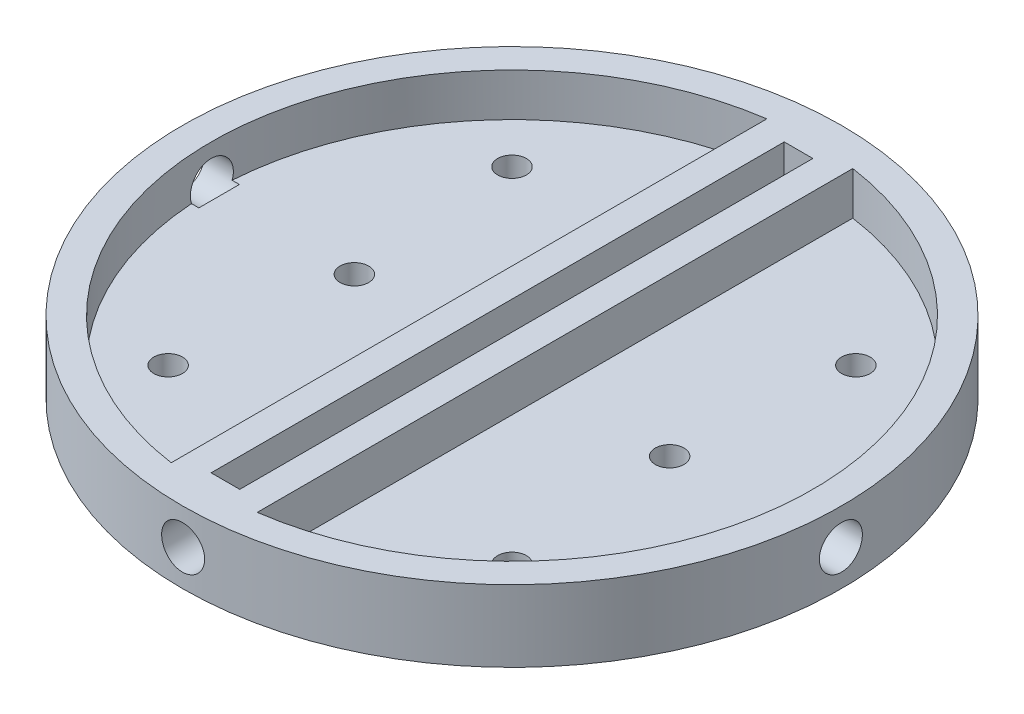
SolidWorks part; units mm, degrees
material "ABS"
ref_plane "Front Plane" through (0, 0, 0) normal (0, 0, 1) x (1, 0, 0)
ref_plane "Top Plane" through (0, 0, 0) normal (0, 1, 0) x (1, 0, 0)
ref_plane "Right Plane" through (0, 0, 0) normal (1, 0, 0) x (0, 0, -1)
sketch "Sketch17" plane through (0, 0, 0) normal (0, 0, 1) x (1, 0, 0)
  line L0 (0, 36.6652) -> (0, -18.0015)
sketch "Sketch5" plane through (0, 0, 0) normal (0, 1, 0) x (1, 0, 0)
  circle A0 centre (0, 0) radius 73.025
  circle A1 centre (38.1, 38.1) radius 3.175
  circle A2 centre (38.1, -38.1) radius 3.175
  circle A3 centre (-38.1, 38.1) radius 3.175
  circle A4 centre (-38.1, -38.1) radius 3.175
extrude "PlateBase" add sketch "Sketch5" along normal blind 6.35
sketch "Sketch6" plane through (0, 6.35, 0) normal (0, 1, 0) x (1, 0, 0)
  line L1 (3.175, 0) -> (3.175, 72.9559)
  line L3 (3.175, 0) -> (3.175, -72.9559)
  line L4 (0, 0) -> (3.175, 0)
  line L5 (-3.175, 0) -> (-3.175, 72.9559)
  line L6 (-9.525, 0) -> (-9.525, 72.4011)
  line L7 (-9.525, 0) -> (-9.525, -72.4011)
  line L8 (-3.175, 0) -> (-3.175, -72.9559)
  line L9 (9.525, 0) -> (9.525, 72.4011)
  line L10 (9.525, 0) -> (9.525, -72.4011)
  circle A0 centre (0, 0) radius 73.025 construction
  circle M4 centre (0, 0) radius 73.025
extrude "PlateTop" add sketch "Sketch6" along normal blind 9.525 contours L8 L5 L6 L7 M4 | L10 L9 L1 L3 M4 region at (6.346, 6.35, 0) region at (-6.346, 6.35, 0)
sketch "Sketch9" plane through (0, 6.35, 0) normal (0, 1, 0) x (1, 0, 0)
  circle A0 centre (0, 0) radius 66.675
  circle A1 centre (0, 0) radius 73.025
extrude "PlateWalls" add sketch "Sketch9" along normal blind 9.525
sketch "Sketch13" plane through (0, 6.35, 0) normal (0, 1, 0) x (1, 0, 0)
  circle A0 centre (34.925, 0) radius 3.175
extrude "RightThruHole" cut sketch "Sketch13" against normal blind 6.35
sketch "Sketch14" plane through (0, 6.35, 0) normal (0, 1, 0) x (1, 0, 0)
  circle A0 centre (-34.925, 0) radius 3.175
extrude "LeftThruHole" cut sketch "Sketch14" against normal blind 6.35
sketch "Sketch15" plane through (0, 6.35, 0) normal (0, 1, 0) x (1, 0, 0)
  line L1 (-3.175, 66.5994) -> (-3.175, -66.5994) construction
  line L2 (-3.175, 63.5) -> (3.175, 63.5)
  line L3 (3.175, -66.5994) -> (3.175, 66.5994) construction
  line L4 (3.175, 63.5) -> (3.175, 66.5994)
  line L5 (-3.175, 66.5994) -> (-3.175, 63.5)
  line L7 (-3.175, -63.5) -> (-3.175, -66.5994)
  line L8 (-3.175, -63.5) -> (3.175, -63.5)
  line L9 (3.175, -63.5) -> (3.175, -66.5994)
  arc A0 (3.175, 66.5994) -> (-3.175, 66.5994) centre (0, 0) ccw construction
  circle A1 centre (0, 0) radius 66.675 construction
  arc A2 (-3.175, 66.5994) -> (3.175, 66.5994) centre (0, 0) cw
  arc A3 (-3.175, -66.5994) -> (3.175, -66.5994) centre (0, 0) ccw
extrude "Boss-Extrude1" add sketch "Sketch15" along normal blind 9.525 from surface starting at face at (0, 6.35, 0)
sketch3d "3DSketch1" plane through (0, 0, 0) normal (0, 0, 1) x (1, 0, 0)
sketch "Sketch16" plane through (0, 0, 73.025) normal (0, 0, 1) x (1, 0, 0)
  line L0 (0, 0) -> (0, 7.9375)
  circle A0 centre (0, 7.9375) radius 4.765
extrude "InsertHole" cut sketch "Sketch16" against normal blind 8.128 contours A0 region at (3.2741, 4.6634, 73.025)
pattern_circular "InsertHoles" count 4 over 360 about axis through (0, 36.6652, 0) along (0, -1, 0) of "InsertHole"
